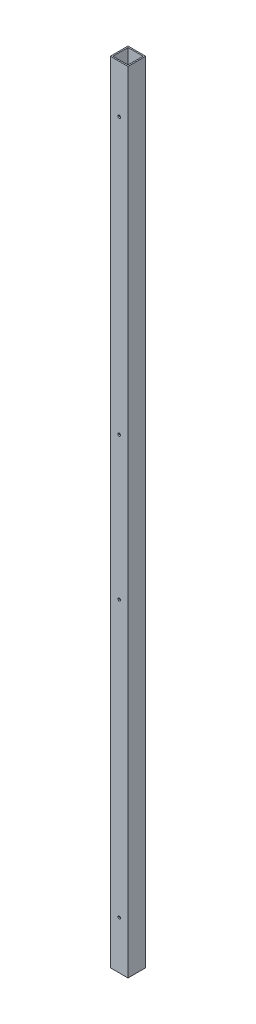
SolidWorks part; units mm, degrees
ref_plane "Front Plane" through (0, 0, 0) normal (0, 0, 1) x (1, 0, 0)
ref_plane "Top Plane" through (0, 0, 0) normal (0, 1, 0) x (1, 0, 0)
ref_plane "Right Plane" through (0, 0, 0) normal (1, 0, 0) x (0, 0, -1)
sketch "Sketch1" plane through (0, 0, 0) normal (0, 1, 0) x (1, 0, 0)
  line L1 (-22.225, -22.225) -> (22.225, -22.225)
  line L2 (-22.225, -22.225) -> (-22.225, 22.225)
  line L3 (-22.225, 22.225) -> (22.225, 22.225)
  line L4 (22.225, -22.225) -> (22.225, 22.225)
  line L5 (-22.225, -22.225) -> (22.225, 22.225) construction
  line L6 (-22.225, 22.225) -> (22.225, -22.225) construction
  line L7 (-19.05, -19.05) -> (19.05, -19.05)
  line L8 (-19.05, -19.05) -> (-19.05, 19.05)
  line L9 (-19.05, 19.05) -> (19.05, 19.05)
  line L10 (19.05, -19.05) -> (19.05, 19.05)
  line L11 (-19.05, -19.05) -> (19.05, 19.05) construction
  line L12 (-19.05, 19.05) -> (19.05, -19.05) construction
  point P0 (0, 0)
  point P6 (0, 0)
  dimension "D1" = 44.45
  dimension "D2" = 3.175
extrude "Boss-Extrude1" add sketch "Sketch1" along normal blind 1984.375
sketch "Sketch2" plane through (0, 0, 22.225) normal (0, 0, 1) x (1, 0, 0)
  line L0 (-22.225, 1984.375) -> (-22.225, 0) construction
  line L1 (-22.225, 992.1875) -> (22.225, 992.1875) construction
  line L2 (22.225, 1984.375) -> (22.225, 0) construction
  point P0 (0, 120.65)
  point P1 (0, 812.8)
  point P9 (0, 1863.725)
  point P10 (0, 1171.575)
  dimension "D1" = 120.65
  dimension "D2" = 692.15
  dimension "D3" = 22.225
hole_wizard "17/64 (0.26563) Diameter Hole1" positions "Sketch3" profile "Sketch4" hole size "17/64" standard "ANSI Inch" end condition through all
sketch "Sketch3" plane through (0, 0, 22.225) normal (0, 0, 1) x (1, 0, 0)
  point P0 (0, 812.8)
  point P3 (0, 120.65)
  point P6 (0, 1171.575)
  point P9 (0, 1863.725)
sketch "Sketch4" plane through (0, 812.8, 22.225) normal (1, 0, 0) x (0, -1, 0)
  line L0 (0, 0) -> (0, 44.45)
  line L1 (0, 44.45) -> (3.3735, 44.45)
  line L2 (3.3735, 44.45) -> (3.3735, 0)
  line L5 (3.3735, 0) -> (0, 0)
  line L11 (0, -6.35) -> (0, 107.95) construction
  dimension "Thru Hole Dia." = 6.747
  dimension "Thru Hole Depth" = 44.45
